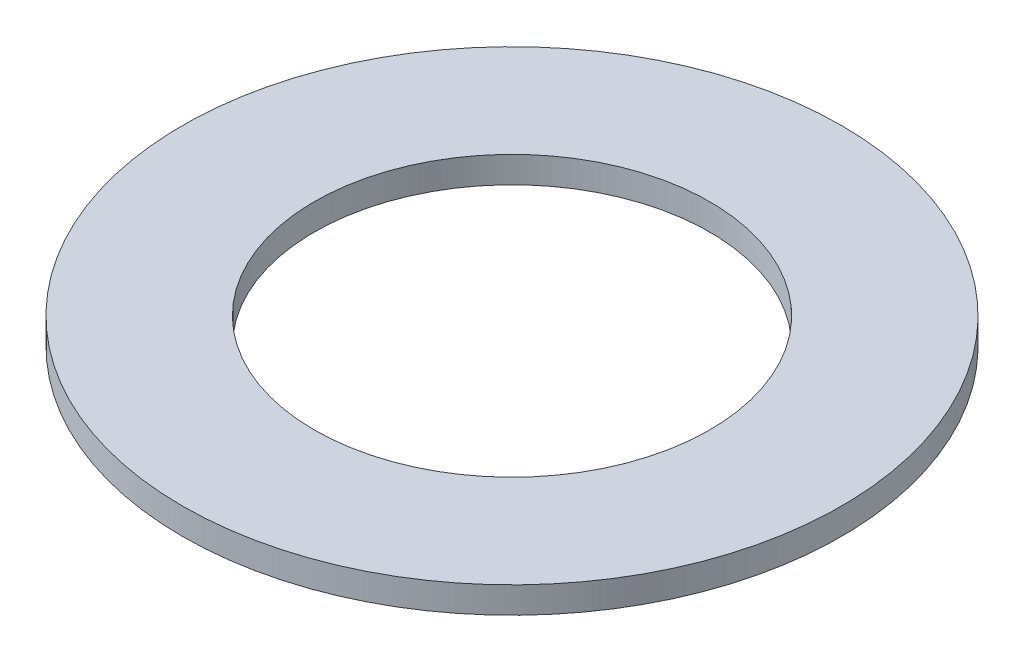
SolidWorks part; units mm, degrees
ref_plane "Front Plane" through (0, 0, 0) normal (0, 0, 1) x (1, 0, 0)
ref_plane "Top Plane" through (0, 0, 0) normal (0, 1, 0) x (1, 0, 0)
ref_plane "Right Plane" through (0, 0, 0) normal (1, 0, 0) x (0, 0, -1)
sketch "Sketch1" plane through (0, 0, 0) normal (0, 1, 0) x (1, 0, 0)
  circle A0 centre (0, 0) radius 75
  dimension "FLANGE_OD" = 150
extrude "Boss-Extrude1" add sketch "Sketch1" along normal blind 6
sketch "Sketch2" plane through (0, 0, 0) normal (0, 1, 0) x (1, 0, 0)
  circle A0 centre (0, 0) radius 45
  dimension "BORE_D" = 90
extrude "Cut-Extrude1" cut sketch "Sketch2" along normal through all
sketch "Sketch3" plane through (0, 6, 0) normal (0, 1, 0) x (1, 0, 0)
  circle A0 centre (0, 0) radius 26.0303 construction
  circle A1 centre (-26.0303, 0) radius 4.9865
  dimension "BOLT_D" = 9.973
  dimension "BOLT_PCD" = 52.0607
extrude "Cut-Extrude2" cut sketch "Sketch3" against normal blind 5.7219 rebuild error yes
pattern_circular "CirPattern1" count 5 over 360 rebuild error yes
